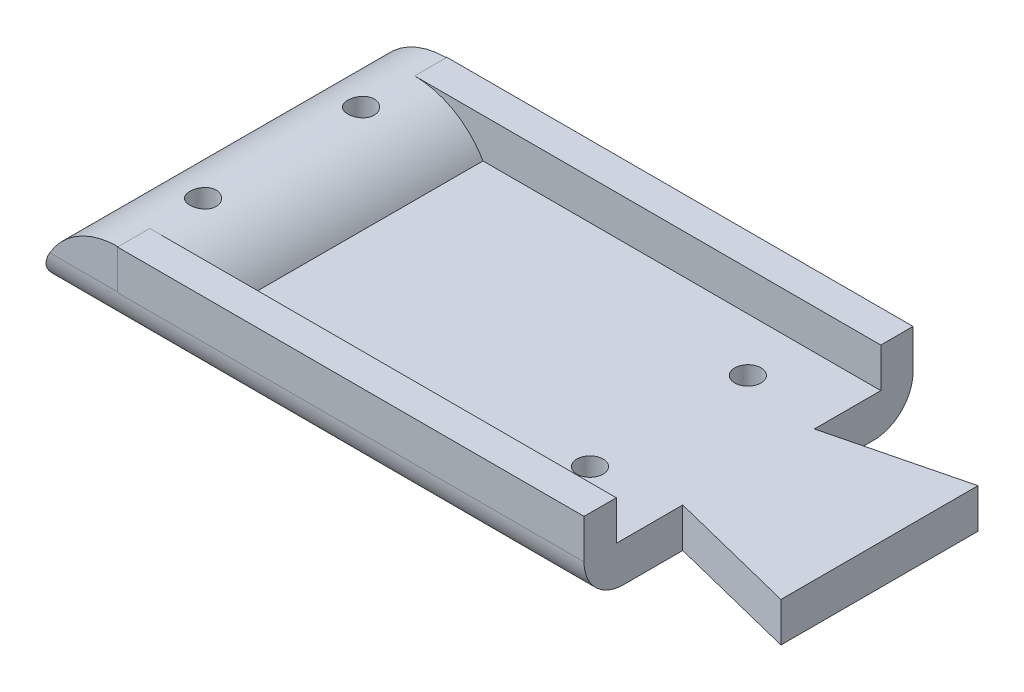
SolidWorks part; units mm, degrees
ref_plane "Alzado" through (0, 0, 0) normal (0, 0, 1) x (1, 0, 0)
ref_plane "Planta" through (0, 0, 0) normal (0, 1, 0) x (1, 0, 0)
ref_plane "Vista lateral" through (0, 0, 0) normal (1, 0, 0) x (0, 0, -1)
sketch "Croquis1" plane through (0, 0, 0) normal (0, 1, 0) x (1, 0, 0)
  line L0 (25.2462, -7.1471) -> (25.2462, 7.8279)
  line L1 (25.2462, 7.8279) -> (15.2962, 5.3404)
  line L2 (15.2962, 5.3404) -> (15.2962, 12.8404)
  line L3 (15.2962, 12.8404) -> (-26.1538, 12.7904)
  line L4 (-26.1538, 12.7904) -> (-26.1538, -12.1096)
  line L5 (-26.1538, -12.1096) -> (15.2962, -12.1596)
  line L6 (15.2962, -12.1596) -> (15.2962, -4.6596)
  line L7 (15.2962, -4.6596) -> (25.2462, -7.1471)
  circle A0 centre (9.2462, 6.3404) radius 1
  circle A1 centre (9.2462, -5.6596) radius 1
  circle A2 centre (-20.1538, -5.6596) radius 1
  circle A3 centre (-20.1538, 6.3404) radius 1
extrude "Saliente-Extruir1" add sketch "Croquis1" along normal blind 3
sketch "Croquis2" plane through (-0.0146, 0, 12.1412) normal (-0.0012, 0, 1) x (1, 0, 0.0012)
  line L0 (-26.1392, 0) -> (15.3108, 0) construction
  line L1 (-26.1392, 3) -> (-26.1392, 0) construction
  line L3 (-25.3353, 3) -> (-14.943, 3)
  line L4 (-26.1392, 3) -> (15.3108, 3) construction
  arc A0 (-14.943, 3) -> (-25.3353, 3) centre (-20.1392, 0) ccw
  dimension "D1" = 12
extrude "Saliente-Extruir2" add sketch "Croquis2" against normal up to surface (24.902 mm away) up to face at (-5.4288, 1.5, -12.8154)
sketch "Croquis3" plane through (0, 3, 0) normal (0, 1, 0) x (1, 0, 0)
  line L1 (15.2962, -12.1596) -> (-20.1538, -12.1596)
  line L2 (15.2962, -12.1596) -> (15.2962, -9.7096)
  line L3 (15.2962, -9.7096) -> (-20.1538, -9.7096)
  line L4 (-20.1538, -12.1596) -> (-20.1538, -9.7096)
  line L5 (15.2962, 12.8404) -> (-20.1538, 12.8404)
  line L6 (15.2962, 12.8404) -> (15.2962, 10.3904)
  line L7 (15.2962, 10.3904) -> (-20.1538, 10.3904)
  line L8 (-20.1538, 12.8404) -> (-20.1538, 10.3904)
  dimension "D1" = 2.45
  dimension "D2" = 35.45
extrude "Saliente-Extruir3" add sketch "Croquis3" along normal blind 3
sketch "Croquis4" plane through (0, 0, 0) normal (0, -1, 0) x (1, 0, 0)
  circle A0 centre (-20.1538, -6.3404) radius 1 construction
  circle A1 centre (-20.1538, 5.6596) radius 1 construction
  circle A2 centre (-20.1538, -6.3404) radius 1
  circle A3 centre (-20.1538, 5.6596) radius 1
extrude "Cortar-Extruir1" cut sketch "Croquis4" against normal blind 17
sketch "Croquis5" plane through (-0.0146, 0, 12.1412) normal (-0.0012, 0, 1) x (1, 0, 0.0012)
  line L0 (-26.1392, 0) -> (15.3108, 0) construction
  line L1 (-20.1392, 6) -> (-20.1392, 8.5495)
  line L2 (-26.1392, 0) -> (-28.6887, 0)
  arc A0 (-20.1392, 6) -> (-26.1392, 0) centre (-20.1392, 0) ccw
  arc A1 (-20.1392, 8.5495) -> (-28.6887, 0) centre (-20.1392, 0) ccw
  dimension "D1" = 12
extrude "Cortar-Extruir2" cut sketch "Croquis5" against normal blind 31
fillet "Redondeo1" radius 3 2 edges at (-5.4288, 0, 12.1346) (-5.4138, 0, -12.8154)
